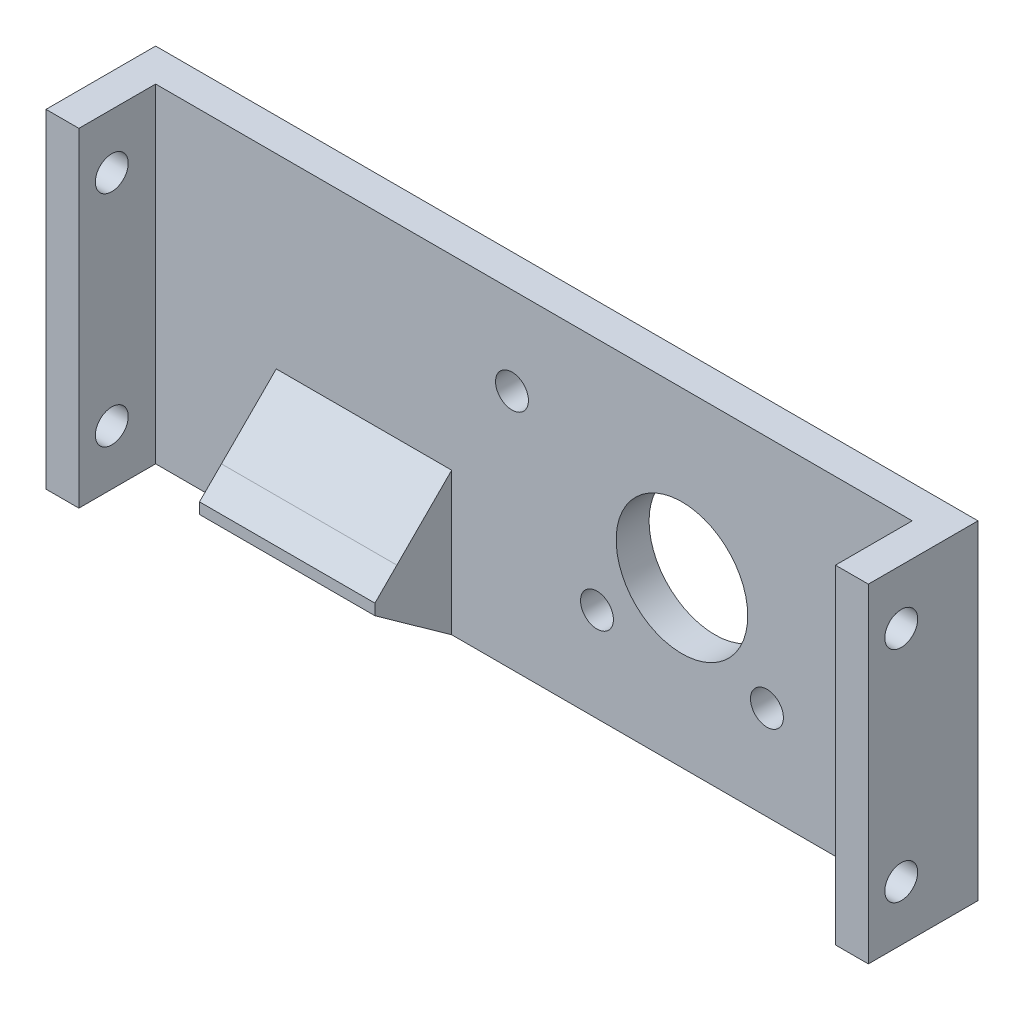
SolidWorks part; units mm, degrees
ref_plane "Front Plane" through (0, 0, 0) normal (0, 0, 1) x (1, 0, 0)
ref_plane "Top Plane" through (0, 0, 0) normal (0, 1, 0) x (1, 0, 0)
ref_plane "Right Plane" through (0, 0, 0) normal (1, 0, 0) x (0, 0, -1)
sketch "Sketch1" plane through (0, 0, 0) normal (0, 0, 1) x (1, 0, 0)
  line L1 (-37.5, -15) -> (37.5, -15)
  line L2 (-37.5, -15) -> (-37.5, 15)
  line L3 (-37.5, 15) -> (37.5, 15)
  line L4 (37.5, -15) -> (37.5, 15)
  line L5 (-37.5, -15) -> (37.5, 15) construction
  line L6 (-37.5, 15) -> (37.5, -15) construction
  point P0 (0, 0)
  dimension "D1" = 30
  dimension "D2" = 75
extrude "Boss-Extrude1" add sketch "Sketch1" along normal blind 3
sketch "Sketch2" plane through (0, 0, 0) normal (0, 0, -1) x (-1, 0, 0)
  line L0 (-37.5, -15) -> (-37.5, 15) construction
  line L1 (-34.5, -15) -> (-37.5, -15)
  line L2 (-34.5, -15) -> (-34.5, 15)
  line L3 (-34.5, 15) -> (-37.5, 15)
  line L4 (-37.5, -15) -> (-37.5, 15)
  line L5 (-34.5, -15) -> (-37.5, 15) construction
  line L6 (-34.5, 15) -> (-37.5, -15) construction
  line L7 (-37.5, 15) -> (37.5, 15) construction
  line L8 (37.5, -15) -> (-37.5, -15) construction
  point P0 (-36, 0)
  dimension "D1" = 0
  dimension "D2" = 0
  dimension "D3" = 3
extrude "Boss-Extrude2" add sketch "Sketch2" against normal blind 10
sketch "Sketch4" plane through (34.5, 0, 0) normal (-1, 0, 0) x (0, 0, 1)
  line L0 (10, 15) -> (3, 15) construction
  line L1 (10, -15) -> (10, 15) construction
  circle A0 centre (7, 10) radius 1.5
  dimension "D1" = 3
  dimension "D2" = 5
  dimension "D3" = 3
extrude "Cut-Extrude1" cut sketch "Sketch4" against normal blind 3
mirror "Mirror2" about plane through (0, 0, 0) normal (0, 1, 0) of "Cut-Extrude1"
mirror "Mirror1" about plane through (0, 0, 0) normal (1, 0, 0) of "Mirror2", "Cut-Extrude1", "Boss-Extrude2"
sketch "Sketch5" plane through (0, 0, 3) normal (0, 0, 1) x (1, 0, 0)
  line L1 (34.5, 15) -> (-34.5, 15) construction
  circle A0 centre (13.5, 0) radius 6
  circle A3 centre (13.5, 7) radius 15.5 construction
  circle A4 centre (13.5, 22.5) radius 1.5 construction
  circle A5 centre (21.25, 20.4234) radius 1.5 construction
  circle A6 centre (5.75, 20.4234) radius 1.5 construction
  circle A7 centre (29, 7) radius 1.5
  circle A8 centre (26.9234, -0.75) radius 1.5 construction
  circle A9 centre (21.25, -6.4234) radius 1.5
  circle A10 centre (5.75, -6.4234) radius 1.5
  circle A11 centre (0.0766, -0.75) radius 1.5 construction
  circle A12 centre (-2, 7) radius 1.5
  point P26 (13.5, 7)
  dimension "D1" = 31
  dimension "D2" = 7
  dimension "D3" = 12
  dimension "D4" = 3
  dimension "D5" = 3
  dimension "D6" = 3
  dimension "D7" = 15
  dimension "D8" = 30
  dimension "D9" = 30
  dimension "D10" = 3
extrude "Cut-Extrude2" cut sketch "Sketch5" against normal blind 10
sketch "Sketch6" plane through (0, -15, 0) normal (0, -1, 0) x (1, 0, 0)
  line L0 (-34.5, 3) -> (34.5, 3) construction
  line L1 (-23.5, 3) -> (-7.5, 3)
  line L2 (-23.5, 3) -> (-23.5, 10)
  line L3 (-23.5, 10) -> (-7.5, 10)
  line L4 (-7.5, 3) -> (-7.5, 10)
  line L5 (-34.5, 10) -> (-34.5, 3) construction
  dimension "D1" = 0
  dimension "D2" = 11
  dimension "D3" = 16
extrude "Boss-Extrude3" add sketch "Sketch6" against normal blind 8
chamfer "Chamfer1" distance 7 distance2 5 1 edges at (-15.5, -15, 10)
sketch "Sketch7" plane through (0, -11.3514, 8.1081) normal (0, -0.8137, 0.5812) x (1, 0, 0)
  line L0 (-23.5, -4.0687) -> (-23.5, -9.9641) construction
  line L1 (-7.5, -9.9641) -> (-7.5, -4.0687) construction
  line L2 (-7.5, -6.2774) -> (-23.5, -6.2774) construction
  circle A0 centre (-19.5, -2.2774) radius 1.5
  circle A1 centre (-11.5, -2.2774) radius 1.5
  dimension "D1" = 3
  dimension "D2" = 3
  dimension "D3" = 4
  dimension "D4" = 4
  dimension "D5" = 4
  dimension "D6" = 4
extrude "Cut-Extrude3" cut sketch "Sketch7" against normal blind 5
chamfer "Chamfer2" distance 5 angle 45 1 edges at (-15.5, -7, 3)
chamfer "Chamfer3" distance 2 angle 45 1 edges at (-15.5, -7, 10)
sketch "Sketch8" plane through (0, -11.3514, 8.1081) normal (0, -0.8137, 0.5812) x (1, 0, 0)
  line L1 (-16.3246, -2.2774) -> (-17.9123, 0.4726)
  line L2 (-17.9123, 0.4726) -> (-21.0877, 0.4726)
  line L3 (-21.0877, 0.4726) -> (-22.6754, -2.2774)
  line L4 (-22.6754, -2.2774) -> (-21.0877, -5.0274)
  line L5 (-21.0877, -5.0274) -> (-17.9123, -5.0274)
  line L6 (-17.9123, -5.0274) -> (-16.3246, -2.2774)
  line L7 (-8.3246, -2.2774) -> (-9.9123, 0.4726)
  line L8 (-9.9123, 0.4726) -> (-13.0877, 0.4726)
  line L9 (-13.0877, 0.4726) -> (-14.6754, -2.2774)
  line L10 (-14.6754, -2.2774) -> (-13.0877, -5.0274)
  line L11 (-13.0877, -5.0274) -> (-9.9123, -5.0274)
  line L12 (-9.9123, -5.0274) -> (-8.3246, -2.2774)
  circle A0 centre (-19.5, -2.2774) radius 2.75 construction
  circle A1 centre (-11.5, -2.2774) radius 2.75 construction
  dimension "D1" = 5.5
  dimension "D2" = 5.5
extrude "Cut-Extrude4" cut sketch "Sketch8" against normal through all from offset 5 offset against normal yes
equation "\"D2@Sketch7\"=\"D1@Sketch7\""
equation "\"D5@Sketch7\"=4"
